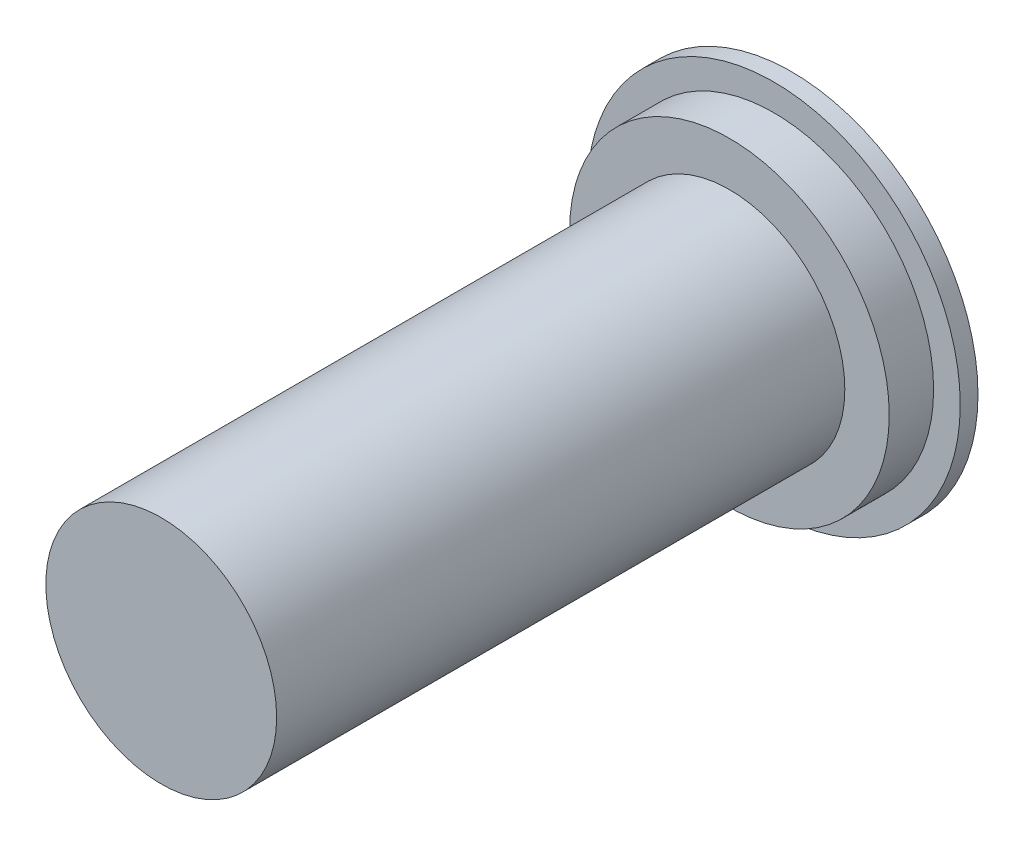
SolidWorks part; units mm, degrees
ref_plane "Front Plane" through (0, 0, 0) normal (0, 0, 1) x (1, 0, 0)
ref_plane "Top Plane" through (0, 0, 0) normal (0, 1, 0) x (1, 0, 0)
ref_plane "Right Plane" through (0, 0, 0) normal (1, 0, 0) x (0, 0, -1)
sketch "Sketch2" plane through (0, 0, 0) normal (0, 0, 1) x (1, 0, 0)
  circle A0 centre (0, 0) radius 20
  circle A1 centre (0, 0) radius 13
  circle A2 centre (0, 0) radius 18
  circle A3 centre (0, 0) radius 21
  circle A4 centre (0, 0) radius 12
  dimension "D1" = 40
  dimension "D2" = 26
  dimension "D3" = 2
  dimension "D4" = 1
  dimension "D5" = 1
extrude "Boss-Extrude1" add sketch "Sketch2" along normal blind 70 contours A1 A4 region at (-12.6323, 0, 0)
extrude "Boss-Extrude2" add sketch "Sketch2<3>" along normal blind 7 contours A2 A1 region at (-17.4909, 0, 0)
sketch "Sketch2<3>" plane through (0, 0, 0) normal (0, 0, 1) x (1, 0, 0) same geometry as "Sketch2"
extrude "Boss-Extrude3" add sketch "Sketch2<4>" along normal blind 2 contours A0 A2 | A3 A0 region at (-19.4343, 0, 0) region at (-20.406, 0, 0)
sketch "Sketch2<4>" plane through (0, 0, 0) normal (0, 0, 1) x (1, 0, 0) same geometry as "Sketch2"
sketch "Sketch3" plane through (0, 0, 70) normal (0, 0, 1) x (1, 0, 0)
  circle A1 centre (0, 0) radius 13
  circle A2 centre (0, 0) radius 13
  dimension "D1" = 0
extrude "Boss-Extrude4" add sketch "Sketch3" along normal blind 1
